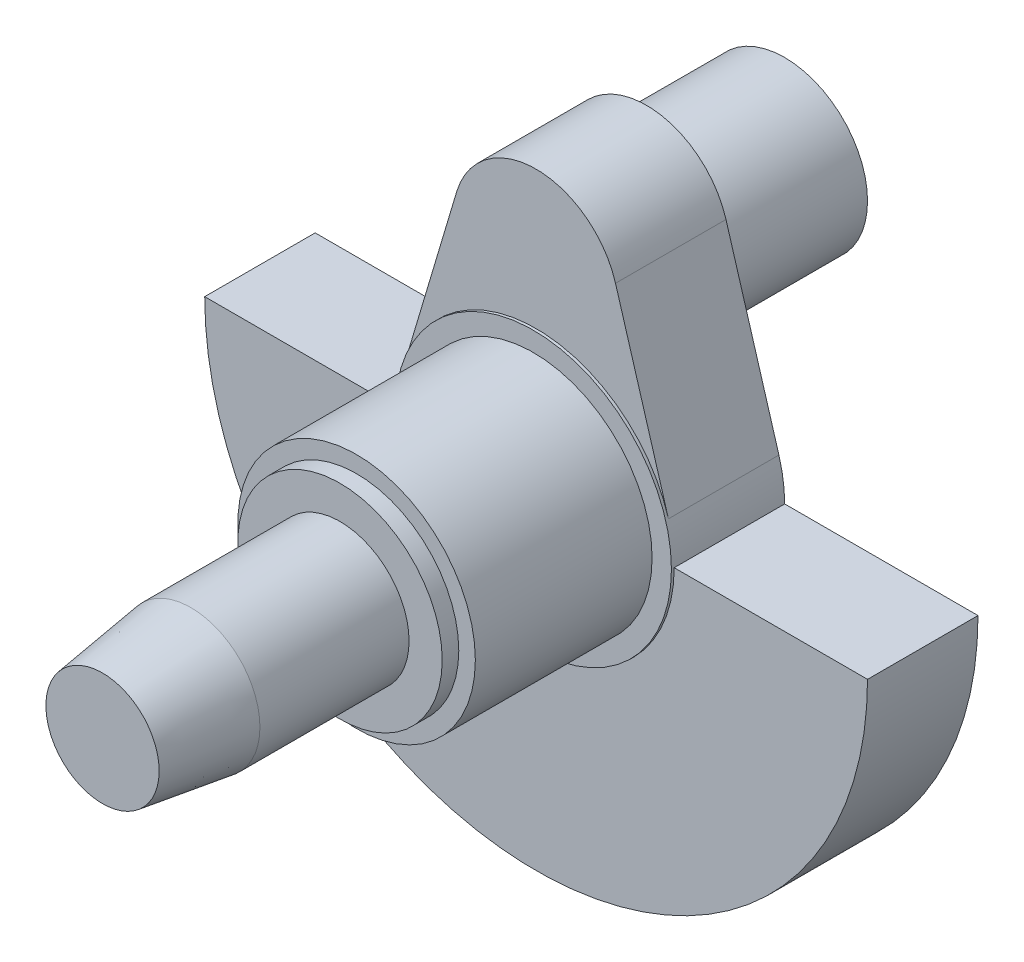
SolidWorks part; units mm, degrees
ref_plane "Front Plane" through (0, 0, 0) normal (0, 0, 1) x (1, 0, 0)
ref_plane "Top Plane" through (0, 0, 0) normal (0, 1, 0) x (1, 0, 0)
ref_plane "Right Plane" through (0, 0, 0) normal (1, 0, 0) x (0, 0, -1)
sketch "Sketch1" plane through (0, 0, 0) normal (0, 0, 1) x (1, 0, 0)
  line L0 (0, 0) -> (0, 70) construction
  line L1 (-28.7494, 78.5714) -> (-47.9157, 14.2857)
  line L2 (28.7494, 78.5714) -> (47.9157, 14.2857)
  line L3 (-41.7399, 35) -> (41.7399, 35) construction
  line L4 (-120, 0) -> (-50, 0)
  line L5 (120, 0) -> (50, 0)
  circle A0 centre (0, 0) radius 50
  arc A1 (-28.7494, 78.5714) -> (28.7494, 78.5714) centre (0, 70) cw
  arc A2 (120, 0) -> (-120, 0) centre (0, 0) cw
  point P10 (0, 35)
  dimension "D1" = 100
  dimension "D2" = 30
  dimension "D4" = 120
  dimension "D3" = 70
extrude "Boss-Extrude1" add sketch "Sketch1" along normal blind 1 and the other way blind 40 contours A0 region at (0, 0, 0)
extrude "Boss-Extrude2" add sketch "Sketch1<3>" against normal up to surface (40 mm away) contours A2 L5 A0 L4 | A1 L1 A0 L2 region at (0, 66.8029, 0) region at (0, -57.171, 0) up to face at (50, 0, -40)
sketch "Sketch1<3>" plane through (0, 0, 0) normal (0, 0, 1) x (1, 0, 0) same geometry as "Sketch1"
sketch "Sketch2" plane through (0, 0, 0) normal (1, 0, 0) x (0, 0, -1)
  line L0 (-1, 0) -> (-1, 43)
  line L1 (-1, 50) -> (-1, -50) construction
  line L2 (-1, 43) -> (-65, 43)
  line L3 (-65, 43) -> (-65, 37)
  line L4 (-65, 37) -> (-71, 37)
  line L5 (-71, 37) -> (-71, 25)
  line L6 (-71, 25) -> (-125, 25)
  line L7 (-125, 25) -> (-125, 0)
  line L8 (-125, 0) -> (-1, 0)
  dimension "D1" = 43
  dimension "D2" = 64
  dimension "D3" = 6
  dimension "D4" = 12
  dimension "D5" = 54
revolve "Revolve1" add sketch "Sketch2" angle 360 about L8
sketch "Sketch3" plane through (0, 0, 125) normal (0, 0, 1) x (1, 0, 0)
  circle A1 centre (0, 0) radius 25
  circle A2 centre (0, 0) radius 25
  dimension "D1" = 0
extrude "Boss-Extrude3" add sketch "Sketch3" along normal blind 32 draft 8
sketch "Sketch4" plane through (0, 0, -40) normal (0, 0, -1) x (-1, 0, 0)
  circle A0 centre (0, 60) radius 30
  arc A2 (28.7494, 78.5714) -> (-28.7494, 78.5714) centre (0, 70) ccw construction
  dimension "D1" = 60
extrude "Boss-Extrude4" add sketch "Sketch4" along normal blind 50
equation "\"D2@Sketch1\"=\"D1@Sketch1\"*.3"
equation "\"D3@Sketch1\"=\"D1@Sketch1\"*.7"
equation "\"D4@Sketch1\"=\"D1@Sketch1\"*1.2"
equation "\"D1@Boss-Extrude1\"=\"D1@Sketch1\"*.01"
equation "\"D2@Boss-Extrude1\"=\"D1@Sketch1\"*.4"
